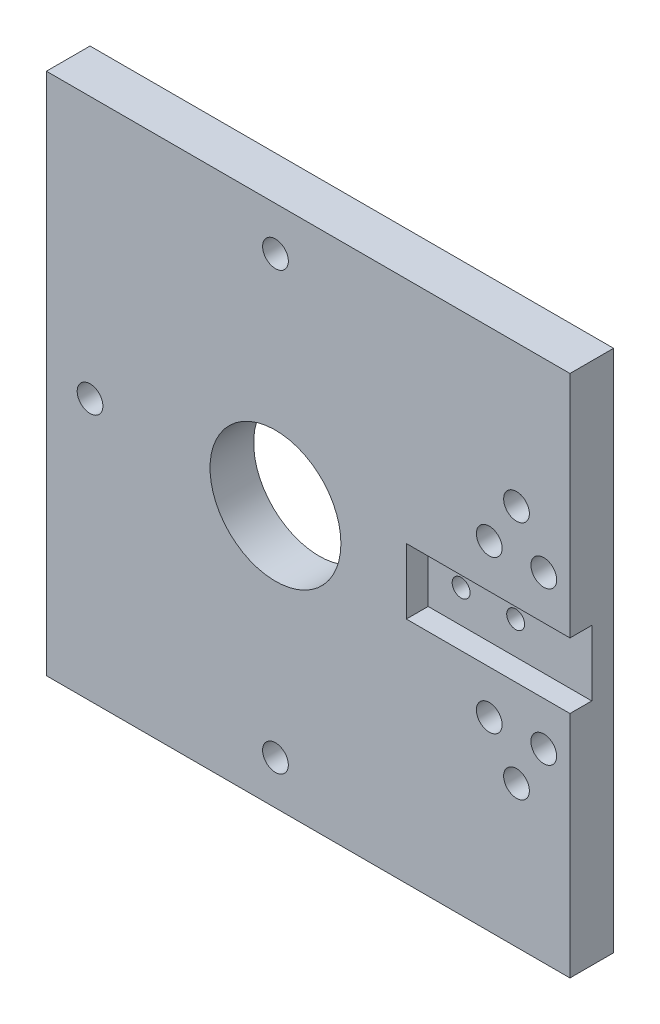
SolidWorks part; units mm, degrees
ref_plane "Alzado" through (0, 0, 0) normal (0, 0, 1) x (1, 0, 0)
ref_plane "Planta" through (0, 0, 0) normal (0, 1, 0) x (1, 0, 0)
ref_plane "Vista lateral" through (0, 0, 0) normal (1, 0, 0) x (0, 0, -1)
sketch "Croquis1" plane through (0, 0, 0) normal (0, 0, 1) x (1, 0, 0)
  line L1 (-67.5, 60) -> (67.5, 60)
  line L2 (-67.5, 60) -> (-67.5, -60)
  line L3 (-67.5, -60) -> (67.5, -60)
  line L4 (67.5, 60) -> (67.5, -60)
  line L5 (-67.5, 60) -> (67.5, -60) construction
  line L6 (-67.5, -60) -> (67.5, 60) construction
  line L7 (67.5, 7.5) -> (30, 7.5)
  line L8 (67.5, 7.5) -> (67.5, -7.5)
  line L9 (67.5, -7.5) -> (30, -7.5)
  line L10 (30, 7.5) -> (30, -7.5)
  line L11 (-67.5, 60) -> (-52.5, 60)
  line L12 (-67.5, 60) -> (-67.5, -60)
  line L13 (-67.5, -60) -> (-52.5, -60)
  line L14 (-52.5, 60) -> (-52.5, -60)
  circle A0 centre (0, 0) radius 15
  circle A1 centre (37.55, 0) radius 2.05
  circle A2 centre (50.05, 0) radius 2.05
  point P0 (0, 0)
  point P12 (30, 0)
  point P13 (67.5, 0)
  dimension "D3" = 30
  dimension "D6" = 7.55
  dimension "D7" = 12.5
  dimension "D8" = 4.1
  dimension "D1" = 135
  dimension "D2" = 120
  dimension "D4" = 15
  dimension "D5" = 37.5
  dimension "D9" = 15
extrude "Saliente-Extruir1" add sketch "Croquis1" along normal blind 5 contours L10 L7 L4 L1 L2 L3 L9 A0 | L7 L10 L9 L4 A2 A1 region at (7.5, 58.3029, 0) region at (67.0961, 0, 0)
extrude "Saliente-Extruir2" add sketch "Croquis1<4>" along normal offset from surface (10 mm away) 5 contours L10 L7 L4 L1 L2 L3 L9 A0 region at (7.5, 58.3029, 0) up to face at (7.5, 0, 5) offset beyond the face yes
sketch "Croquis1<4>" plane through (0, 0, 0) normal (0, 0, 1) x (1, 0, 0) same geometry as "Croquis1"
sketch "Croquis2" plane through (0, 0, 10) normal (0, 0, 1) x (1, 0, 0)
  line L0 (49, 17.5) -> (61.5, 17.5) construction
  line L1 (67.5, 60) -> (67.5, 7.5) construction
  line L3 (67.5, 7.5) -> (30, 7.5) construction
  line L4 (0, 0) -> (100.8416, 0) construction
  line L5 (49, -17.5) -> (61.5, -17.5) construction
  line L6 (-52.5, 60) -> (-52.5, -60) construction
  line L7 (-52.5, 60) -> (67.5, 60) construction
  circle A0 centre (49, 17.5) radius 2.95
  circle A1 centre (55.25, 27.5) radius 2.95
  circle A2 centre (61.5, 17.5) radius 2.95
  circle A3 centre (61.5, -17.5) radius 2.95
  circle A4 centre (55.25, -27.5) radius 2.95
  circle A5 centre (49, -17.5) radius 2.95
  circle A6 centre (-42.5, 0) radius 2.95
  circle A7 centre (0, 50) radius 2.95
  circle A9 centre (0, -50) radius 2.95
  point P5 (55.25, 17.5)
  point P31 (0, 0)
  dimension "D1" = 5.9
  dimension "D6" = 5.9
  dimension "D7" = 10
  dimension "D8" = 10
  dimension "D2" = 12.5
  dimension "D3" = 6
  dimension "D4" = 10
  dimension "D5" = 10
extrude "Cortar-Extruir1" cut sketch "Croquis2" against normal through all
